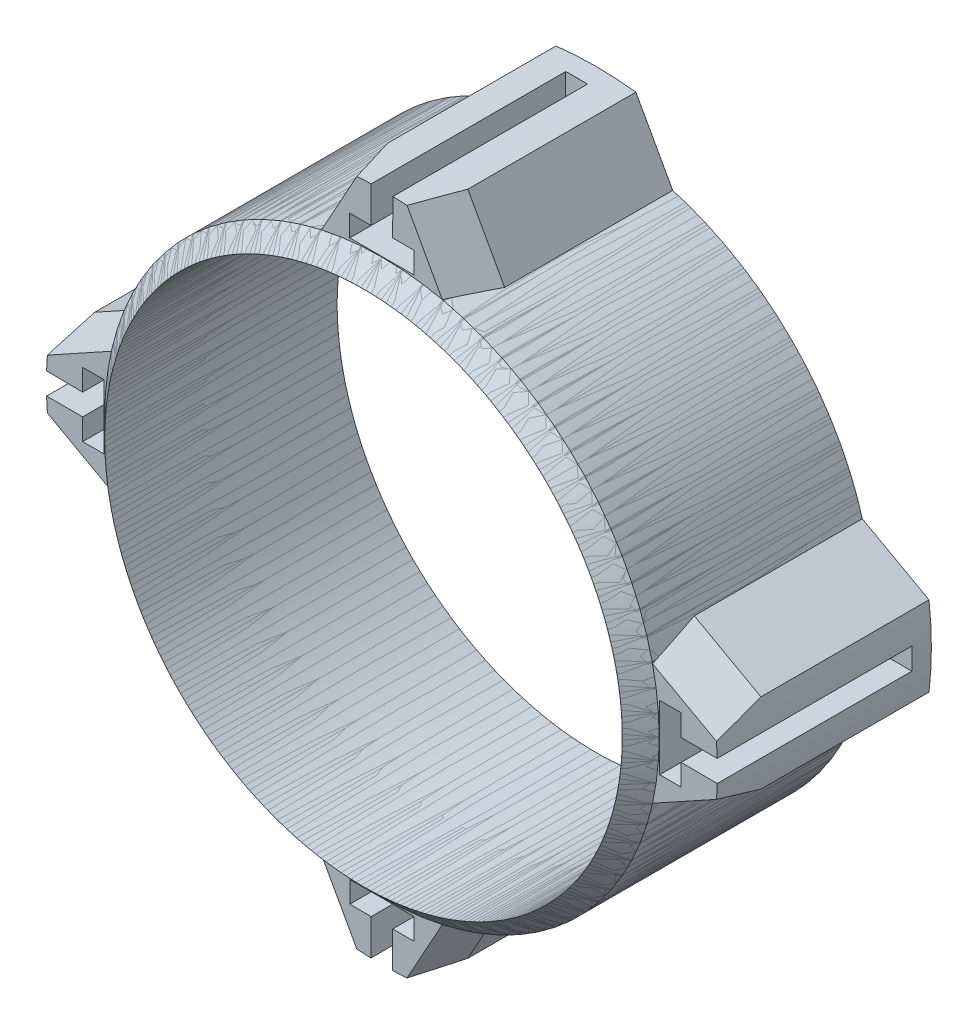
SolidWorks part; units mm, degrees
note: '?' marks a value the reader was unsure of.
ref_plane "Front Plane" through (0, 0, 0) normal (0, 0, 1) x (1, 0, 0)
ref_plane "Top Plane" through (0, 0, 0) normal (0, 1, 0) x (1, 0, 0)
ref_plane "Right Plane" through (0, 0, 0) normal (1, 0, 0) x (0, 0, -1)
sketch "Sketch1" plane through (0, 0, 0) normal (0, 0, 1) x (1, 0, 0)
  circle A0 centre (0, 0) radius 84.5
  circle A1 centre (0, 0) radius 90.5
  dimension "D1" = 169
  dimension "D2" = 181
extrude "Boss-Extrude1" add sketch "Sketch1" along normal blind 76.35
sketch "Sketch2" plane through (0, 0, 76.35) normal (0, 0, 1) x (1, 0, 0)
ref_axis "Axis1" through (0, 0, 76.35) along (0, 0, -1)?
chamfer "Chamfer1" distance 6.5 angle 45 1 edges at (90.5, 0, 76.35)
ref_plane "Plane1" through (90.5, 0, 0) normal (1, 0, 0) x (0, 0, -1)
sketch "Sketch4" plane through (90.5, 0, 0) normal (1, 0, 0) x (0, 0, -1)
  line L0 (-69.85, -90.5) -> (-69.85, 90.5) construction
  line L1 (-69.85, 25.4001) -> (0, 25.4001)
  line L2 (-69.85, 25.4001) -> (-69.85, -25.3999)
  line L3 (-69.85, -25.3999) -> (0, -25.3999)
  line L4 (0, 25.4001) -> (0, -25.3999)
  dimension "D1" = 69.85
  dimension "D2" = 50.8
wrap "Wrap12" sketch "Sketch4" wrap type emboss source sketch "Sketch4" thickness 19 face at (90.5, 0, 69.85) parameters "D1"=19
sketch "Sketch12" plane through (0, 0, 69.85) normal (0, 0, 1) x (1, 0, 0)
  line L1 (122.7067, -0.2012) -> (122.7067, 3.5079)
  line L2 (97.6714, 3.5079) -> (97.6714, 10.5031)
  line L3 (97.6714, 10.5031) -> (90.6686, 10.5031)
  line L4 (90.6686, 10.5031) -> (90.6686, -10.4921)
  line L5 (90.6686, -10.4921) -> (97.6714, -10.4921)
  line L6 (97.6714, 3.5079) -> (122.7067, 3.5079)
  line L7 (122.7067, -0.2012) -> (122.7067, -3.7041)
  line L8 (122.7067, -3.7041) -> (97.6714, -3.4921)
  line L9 (97.6714, -3.4921) -> (97.6714, -10.4921)
  dimension "D1" = 7
  dimension "D2" = 3.5029
  dimension "D3" = 3.7091
  dimension "D4" = 20.9953
extrude "Cut-Extrude1" cut sketch "Sketch12" against normal blind 63.5 contours L7 L8 L9 L5 L4 L3 L2 L6 L1
chamfer "Chamfer2" distance 19 angle 45 2 edges at (105.2155, -30.3306, 34.925) (105.2155, 30.3308, 34.925)
chamfer "Chamfer5" distance 15 angle 15 2 edges at (97.8395, -19.0566, 69.85) (97.8395, 19.0568, 69.85)
pattern_circular "CirPattern6" count 4 over 360 about axis through (0, 0, 0) along (0, 0, 1) of bodies 104
sketch "Sketch13" [suppressed] plane through (-0.0226, -2.6651, 0) normal (0.0085, 1, 0) x (1, -0.0085, 0)
sketch "Sketch14" plane through (0, 0, 0) normal (0, 0, -1) x (-1, 0, 0)
